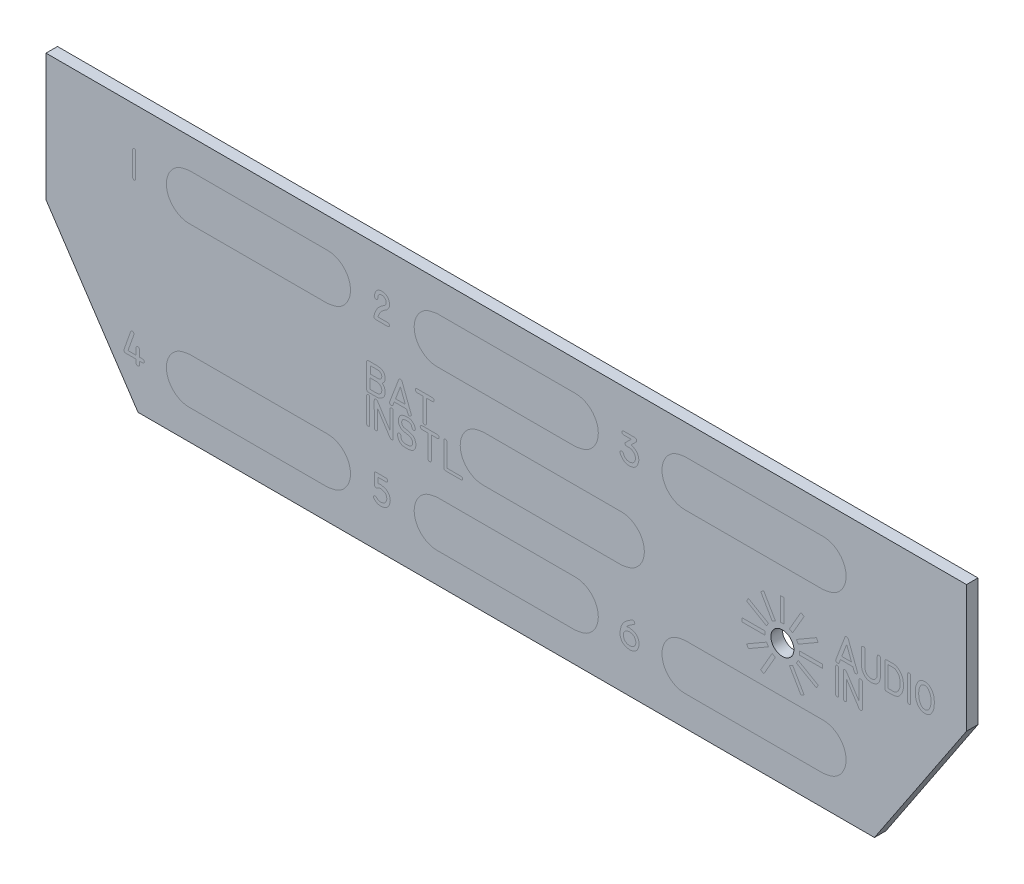
SolidWorks part; units mm, degrees
ref_plane "Front Plane" through (0, 0, 0) normal (0, 0, 1) x (1, 0, 0)
ref_plane "Top Plane" through (0, 0, 0) normal (0, 1, 0) x (1, 0, 0)
ref_plane "Right Plane" through (0, 0, 0) normal (1, 0, 0) x (0, 0, -1)
sketch "Sketch1" plane through (0, 0, 0) normal (0, 0, 1) x (1, 0, 0)
  line L12 (22.225, 2.286) -> (123.825, 2.286)
  line L13 (123.825, 2.286) -> (136.525, 21.336)
  line L14 (136.525, 21.336) -> (136.525, 38.862)
  line L15 (136.525, 38.862) -> (9.525, 38.862)
  line L16 (9.525, 38.862) -> (9.525, 21.336)
  line L17 (9.525, 21.336) -> (22.225, 2.286)
extrude "Boss-Extrude1" add sketch "Sketch1" along normal blind 1.5875
sketch "Sketch2" plane through (0, 0, 1.5875) normal (0, 0, 1) x (1, 0, 0)
  line L0 (73.025, 38.862) -> (73.025, 31.5468) construction
  line L1 (136.525, 38.862) -> (9.525, 38.862) construction
  line L2 (73.025, 31.5468) -> (73.025, 24.2316) construction
  line L3 (73.025, 24.2316) -> (73.025, 16.9164) construction
  line L4 (73.025, 16.9164) -> (73.025, 9.6012) construction
  line L5 (73.025, 9.6012) -> (73.025, 2.286) construction
  line L6 (22.225, 2.286) -> (123.825, 2.286) construction
  line L7 (63.5, 9.6012) -> (82.55, 9.6012) construction
  line L8 (63.5, 12.7762) -> (82.55, 12.7762)
  line L9 (63.5, 6.4262) -> (82.55, 6.4262)
  line L10 (63.5, 31.5468) -> (82.55, 31.5468) construction
  line L11 (63.5, 34.7218) -> (82.55, 34.7218)
  line L12 (63.5, 28.3718) -> (82.55, 28.3718)
  line L13 (60.325, 9.6012) -> (17.3482, 9.6012) construction
  line L14 (9.525, 21.336) -> (22.225, 2.286) construction
  line L15 (29.3116, 9.6012) -> (48.3616, 9.6012) construction
  line L16 (29.3116, 12.7762) -> (48.3616, 12.7762)
  line L17 (29.3116, 6.4262) -> (48.3616, 6.4262)
  line L18 (60.325, 31.5468) -> (9.525, 31.5468) construction
  line L19 (9.525, 38.862) -> (9.525, 21.336) construction
  line L20 (29.3116, 31.5468) -> (48.3616, 31.5468) construction
  line L21 (29.3116, 34.7218) -> (48.3616, 34.7218)
  line L22 (29.3116, 28.3718) -> (48.3616, 28.3718)
  line L23 (73.025, 20.574) -> (79.375, 20.574) construction
  line L24 (88.9, 20.574) -> (69.85, 20.574) construction
  line L25 (88.9, 17.399) -> (69.85, 17.399)
  line L26 (88.9, 23.749) -> (69.85, 23.749)
  line L27 (116.7384, 31.5468) -> (97.6884, 31.5468) construction
  line L28 (116.7384, 34.7218) -> (97.6884, 34.7218)
  line L29 (116.7384, 28.3718) -> (97.6884, 28.3718)
  line L30 (116.7384, 9.6012) -> (97.6884, 9.6012) construction
  line L31 (116.7384, 12.7762) -> (97.6884, 12.7762)
  line L32 (116.7384, 6.4262) -> (97.6884, 6.4262)
  line L33 (21.7424, 31.5468) -> (21.7424, 29.7688) construction
  line L34 (19.3612, 29.7688) -> (24.1237, 29.7688) construction
  line L35 (48.3616, 28.3718) -> (63.5, 28.3718) construction
  line L36 (55.9308, 28.3718) -> (55.9308, 29.7688) construction
  line L37 (53.5496, 29.7688) -> (58.3121, 29.7688) construction
  line L38 (82.55, 28.3718) -> (97.6884, 28.3718) construction
  line L39 (90.1192, 28.3718) -> (90.1192, 29.7688) construction
  line L40 (87.738, 29.7688) -> (92.5005, 29.7688) construction
  line L41 (19.3612, 7.8232) -> (24.1237, 7.8232) construction
  line L42 (53.5496, 7.8232) -> (58.3121, 7.8232) construction
  line L43 (92.5005, 7.8232) -> (87.738, 7.8232) construction
  line L44 (53.5496, 22.352) -> (53.5496, 16.51) construction
  line L45 (53.5496, 20.574) -> (65.0729, 20.574) construction
  line L46 (53.5496, 16.51) -> (65.0729, 16.51) construction
  line L47 (111.125, 21.5447) -> (111.125, 24.7197) construction
  line L48 (111.379, 21.5447) -> (111.379, 24.7197)
  line L49 (110.871, 21.5447) -> (110.871, 24.7197)
  line L50 (111.379, 21.5447) -> (110.871, 21.5447)
  line L51 (111.379, 24.7197) -> (110.871, 24.7197)
  line L52 (112.5356, 21.0986) -> (114.1231, 23.8483)
  line L53 (112.0957, 21.3526) -> (113.6832, 24.1023)
  line L54 (112.5356, 21.0986) -> (112.0957, 21.3526)
  line L55 (114.1231, 23.8483) -> (113.6832, 24.1023)
  line L56 (113.3142, 20.1341) -> (116.0639, 21.7216)
  line L57 (113.0602, 20.574) -> (115.8099, 22.1615)
  line L58 (113.3142, 20.1341) -> (113.0602, 20.574)
  line L59 (116.0639, 21.7216) -> (115.8099, 22.1615)
  line L60 (113.5063, 18.9094) -> (116.6813, 18.9094)
  line L61 (113.5063, 19.4174) -> (116.6813, 19.4174)
  line L62 (113.5063, 18.9094) -> (113.5063, 19.4174)
  line L63 (116.6813, 18.9094) -> (116.6813, 19.4174)
  line L64 (113.0602, 17.7528) -> (115.8099, 16.1653)
  line L65 (113.3142, 18.1928) -> (116.0639, 16.6053)
  line L66 (113.0602, 17.7528) -> (113.3142, 18.1928)
  line L67 (115.8099, 16.1653) -> (116.0639, 16.6053)
  line L68 (112.0957, 16.9742) -> (113.6832, 14.2246)
  line L69 (112.5356, 17.2282) -> (114.1231, 14.4786)
  line L70 (112.0957, 16.9742) -> (112.5356, 17.2282)
  line L71 (113.6832, 14.2246) -> (114.1231, 14.4786)
  line L72 (110.871, 16.7822) -> (110.871, 13.6072) [skipped]
  line L73 (111.379, 16.7822) -> (111.379, 13.6072) [skipped]
  line L74 (110.871, 16.7822) -> (111.379, 16.7822) [skipped]
  line L75 (110.871, 13.6072) -> (111.379, 13.6072) [skipped]
  line L76 (109.7144, 17.2282) -> (108.1269, 14.4786)
  line L77 (110.1543, 16.9742) -> (108.5668, 14.2246)
  line L78 (109.7144, 17.2282) -> (110.1543, 16.9742)
  line L79 (108.1269, 14.4786) -> (108.5668, 14.2246)
  line L80 (108.9358, 18.1928) -> (106.1861, 16.6053)
  line L81 (109.1898, 17.7528) -> (106.4401, 16.1653)
  line L82 (108.9358, 18.1928) -> (109.1898, 17.7528)
  line L83 (106.1861, 16.6053) -> (106.4401, 16.1653)
  line L84 (108.7438, 19.4174) -> (105.5688, 19.4174)
  line L85 (108.7438, 18.9094) -> (105.5688, 18.9094)
  line L86 (108.7438, 19.4174) -> (108.7438, 18.9094)
  line L87 (105.5688, 19.4174) -> (105.5688, 18.9094)
  line L88 (109.1898, 20.574) -> (106.4401, 22.1615)
  line L89 (108.9358, 20.1341) -> (106.1861, 21.7216)
  line L90 (109.1898, 20.574) -> (108.9358, 20.1341)
  line L91 (106.4401, 22.1615) -> (106.1861, 21.7216)
  line L92 (110.1543, 21.3526) -> (108.5668, 24.1023)
  line L93 (109.7144, 21.0986) -> (108.1269, 23.8483)
  line L94 (110.1543, 21.3526) -> (109.7144, 21.0986)
  line L95 (108.5668, 24.1023) -> (108.1269, 23.8483)
  line L96 (118.2688, 21.8168) -> (118.2688, 16.51) construction
  line L97 (118.2688, 19.1634) -> (116.6813, 19.1634) construction
  line L98 (118.2688, 16.51) -> (131.5548, 16.51) construction
  line L99 (118.2688, 20.574) -> (133.3905, 20.574) construction
  arc A0 (63.5, 12.7762) -> (63.5, 6.4262) centre (63.5, 9.6012) ccw
  arc A1 (82.55, 6.4262) -> (82.55, 12.7762) centre (82.55, 9.6012) ccw
  arc A2 (63.5, 34.7218) -> (63.5, 28.3718) centre (63.5, 31.5468) ccw
  arc A3 (82.55, 28.3718) -> (82.55, 34.7218) centre (82.55, 31.5468) ccw
  arc A4 (29.3116, 12.7762) -> (29.3116, 6.4262) centre (29.3116, 9.6012) ccw
  arc A5 (48.3616, 6.4262) -> (48.3616, 12.7762) centre (48.3616, 9.6012) ccw
  arc A6 (29.3116, 34.7218) -> (29.3116, 28.3718) centre (29.3116, 31.5468) ccw
  arc A7 (48.3616, 28.3718) -> (48.3616, 34.7218) centre (48.3616, 31.5468) ccw
  arc A8 (88.9, 17.399) -> (88.9, 23.749) centre (88.9, 20.574) ccw
  arc A9 (69.85, 23.749) -> (69.85, 17.399) centre (69.85, 20.574) ccw
  arc A10 (116.7384, 34.7218) -> (116.7384, 28.3718) centre (116.7384, 31.5468) cw
  arc A11 (97.6884, 28.3718) -> (97.6884, 34.7218) centre (97.6884, 31.5468) cw
  arc A12 (116.7384, 12.7762) -> (116.7384, 6.4262) centre (116.7384, 9.6012) cw
  arc A13 (97.6884, 6.4262) -> (97.6884, 12.7762) centre (97.6884, 9.6012) cw
  circle A14 centre (111.125, 19.1634) radius 2.3813 construction
  text T0 "2"
  text T1 "1"
  text T2 "3"
  text T3 "4"
  text T4 "5"
  text T5 "6"
  text T6 "BAT"
  text T7 "INSTL"
  text T8 "AUDIO"
  text T9 "IN"
  point P12 (73.025, 9.6012)
  point P19 (73.025, 31.5468)
  point P30 (38.8366, 9.6012)
  point P41 (38.8366, 31.5468)
  point P50 (79.375, 20.574)
  point P57 (107.2134, 31.5468)
  point P64 (107.2134, 9.6012)
  point P74 (21.7424, 29.7688)
  point P80 (55.9308, 29.7688)
  point P89 (90.1192, 29.7688)
  point P157 (111.125, 19.1634)
  point P162 (131.5548, 16.51)
  point P165 (112.3026, 20.4814)
  point P166 (112.0878, 19.7815)
  point P167 (0, 0)
  dimension "D11" = 4.7625
  dimension "D1" = 19.05
  dimension "D2" = 6.35
  dimension "D3" = 6.35
  dimension "D4" = 4.7625
  dimension "D5" = 7.5692
  dimension "D6" = 1.778
  dimension "D7" = 7.5692
  dimension "D8" = 1.778
  dimension "D9" = 4.064
  dimension "D10" = 1.778
  dimension "D16" = 1.5875
  dimension "D12" = 22.225
  dimension "D17" = 3.175
  dimension "D13" = 0.254
  dimension "D14" = 0.254
  dimension "D15" = 12
wrap "Wrap3" sketch "Sketch2" wrap type scribe source sketch "Sketch2"
sketch "Sketch3" plane through (0, 0, 1.5875) normal (0, 0, 1) x (1, 0, 0)
  line L0 (112.3156, 17.1012) -> (109.9344, 21.2256) construction
  line L1 (112.0957, 16.9742) -> (112.5356, 17.2282) construction
  line L2 (110.1543, 21.3526) -> (109.7144, 21.0986) construction
  circle A0 centre (111.125, 19.1634) radius 1.5875
  dimension "D1" = 3.175
extrude "Cut-Extrude1" cut sketch "Sketch3" against normal up to next
equation "\"D5@Sketch2\"=\"D7@Sketch2\""
equation "\"D8@Sketch2\"=\"D6@Sketch2\""
